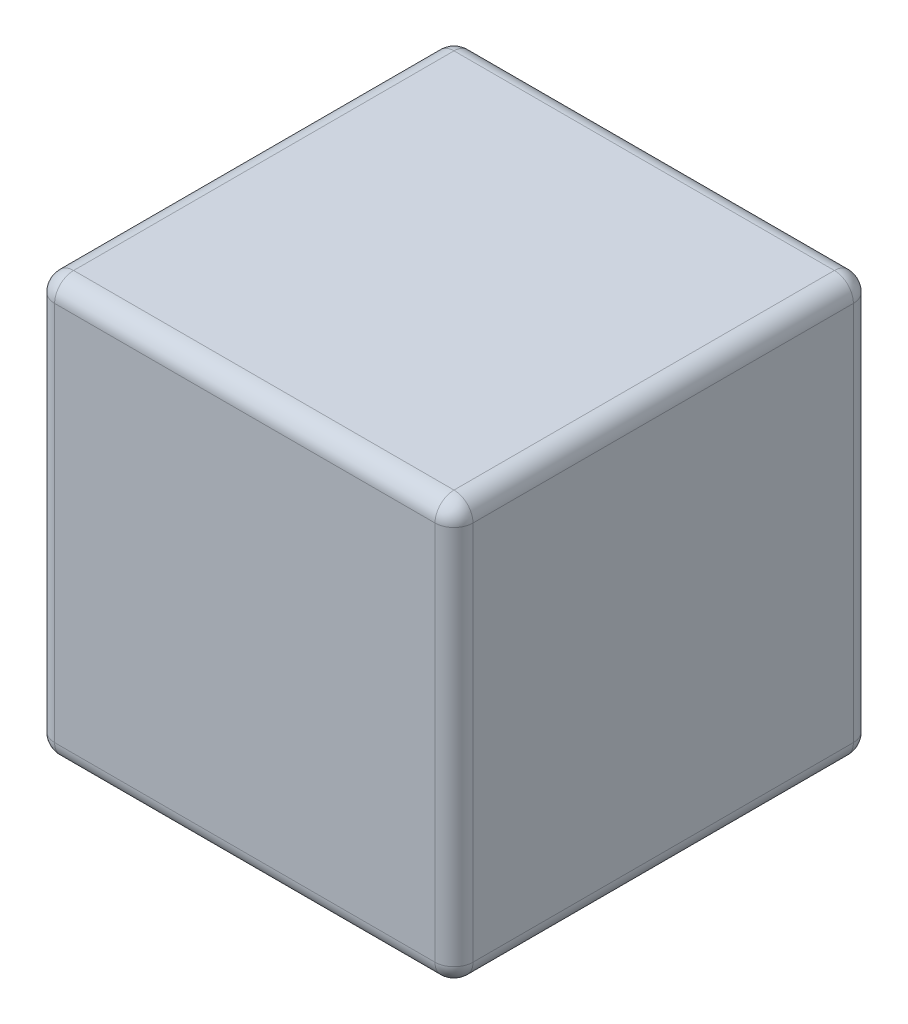
SolidWorks part; units mm, degrees
ref_plane "Front Plane" through (0, 0, 0) normal (0, 0, 1) x (1, 0, 0)
ref_plane "Top Plane" through (0, 0, 0) normal (0, 1, 0) x (1, 0, 0)
ref_plane "Right Plane" through (0, 0, 0) normal (1, 0, 0) x (0, 0, -1)
sketch "Sketch1" plane through (0, 0, 0) normal (0, 1, 0) x (1, 0, 0)
  line L1 (-27.5, 27.5) -> (27.5, 27.5)
  line L2 (-27.5, 27.5) -> (-27.5, -27.5)
  line L3 (-27.5, -27.5) -> (27.5, -27.5)
  line L4 (27.5, 27.5) -> (27.5, -27.5)
  line L5 (-27.5, 27.5) -> (27.5, -27.5) construction
  line L6 (-27.5, -27.5) -> (27.5, 27.5) construction
  point P0 (0, 0)
  dimension "D1" = 55
  dimension "D2" = 55
extrude "Boss-Extrude1" add sketch "Sketch1" along normal blind 27.5 and the other way blind 27.5
fillet "Fillet1" radius 2.5 12 edges at (-27.5, -27.5, 0) (-27.5, 27.5, 0) (0, -27.5, -27.5) (0, 27.5, -27.5) (-27.5, 0, -27.5) (27.5, -27.5, 0) (27.5, 27.5, 0) (27.5, 0, -27.5) (0, -27.5, 27.5) (-27.5, 0, 27.5) (0, 27.5, 27.5) (27.5, 0, 27.5)
